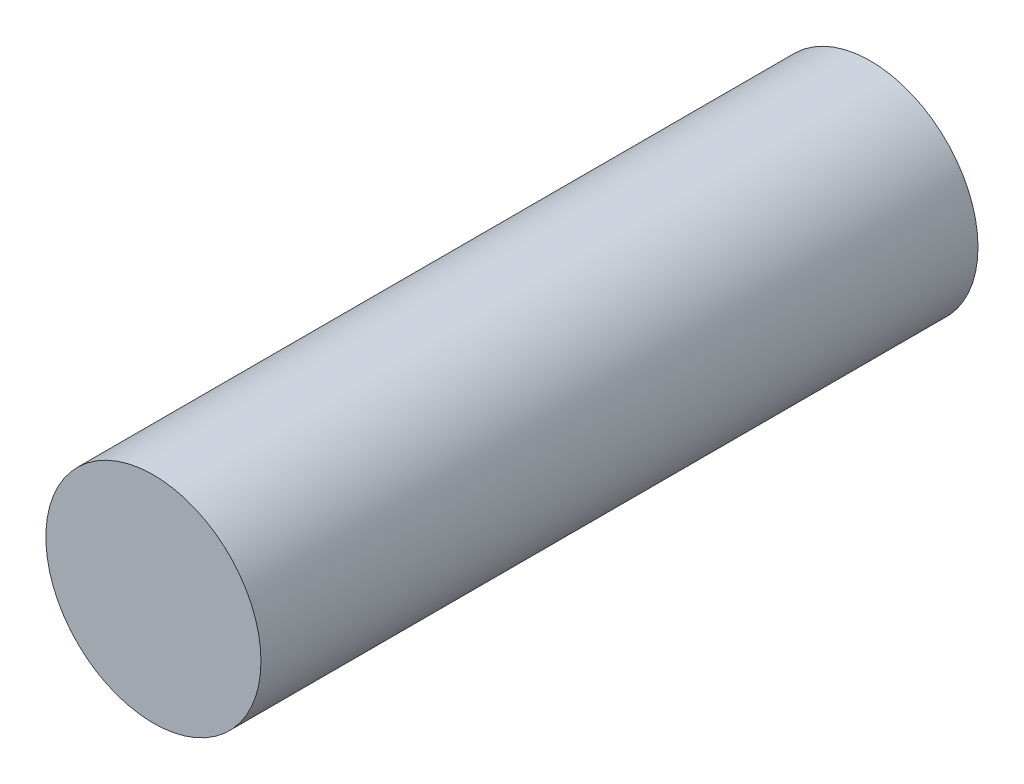
SolidWorks part; units mm, degrees
ref_plane "Front Plane" through (0, 0, 0) normal (0, 0, 1) x (1, 0, 0)
ref_plane "Top Plane" through (0, 0, 0) normal (0, 1, 0) x (1, 0, 0)
ref_plane "Right Plane" through (0, 0, 0) normal (1, 0, 0) x (0, 0, -1)
sketch "Sketch1" plane through (0, 0, 0) normal (0, 0, 1) x (1, 0, 0)
  circle A0 centre (0, 0) radius 1.5
  dimension "D1" = 3
extrude "Boss-Extrude1" add sketch "Sketch1" along normal mid plane 10
other "CPoint1" parameters "Diameter"=1, "StubLength"=1.5
ref_axis "Axis1" through (0, 0, 15) along (0, 0, -1)
other "CPoint2" parameters "Diameter"=1, "StubLength"=1.5
ref_axis "Axis2" through (0, 0, -15) along (0, 0, 1)
